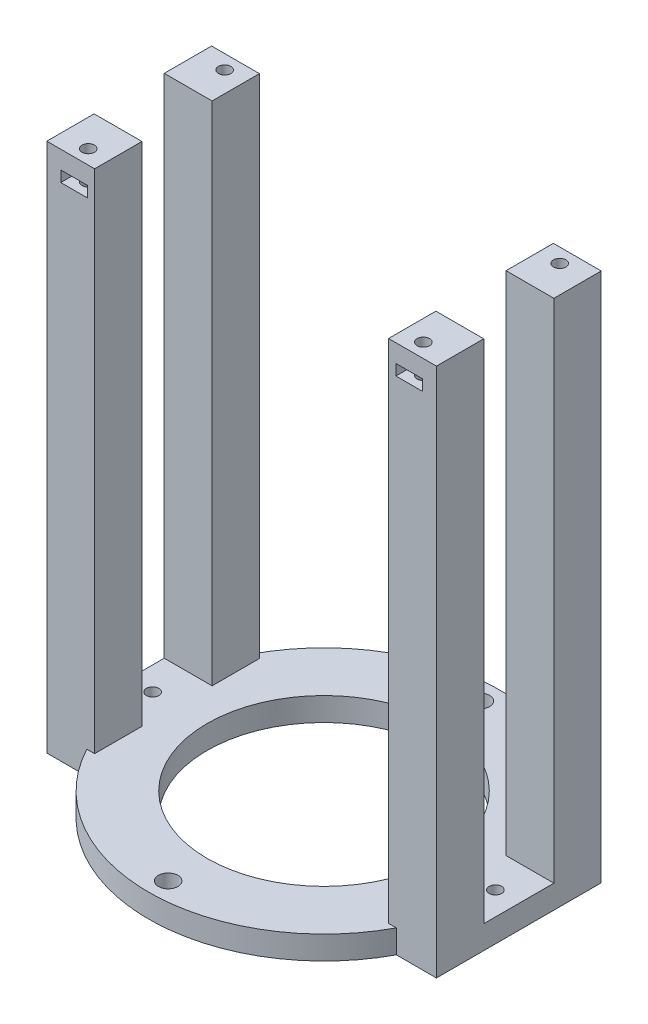
SolidWorks part; units mm, degrees
ref_plane "Front Plane" through (0, 0, 0) normal (0, 0, 1) x (1, 0, 0)
ref_plane "Top Plane" through (0, 0, 0) normal (0, 1, 0) x (1, 0, 0)
ref_plane "Right Plane" through (0, 0, 0) normal (1, 0, 0) x (0, 0, -1)
sketch "Sketch1" plane through (0, 0, 0) normal (0, 1, 0) x (1, 0, 0)
  line L0 (33, 0) -> (-33, 0) construction
  line L2 (-16, 21.15) -> (-50, 21.15)
  line L3 (-16, 21.15) -> (-16, -21.15)
  line L4 (-16, -21.15) -> (-50, -21.15)
  line L5 (-50, 21.15) -> (-50, -21.15)
  line L6 (-16, 21.15) -> (-50, -21.15) construction
  line L7 (-16, -21.15) -> (-50, 21.15) construction
  line L8 (16, 21.15) -> (50, 21.15)
  line L9 (16, 21.15) -> (16, -21.15)
  line L10 (16, -21.15) -> (50, -21.15)
  line L11 (50, 21.15) -> (50, -21.15)
  line L12 (16, 21.15) -> (50, -21.15) construction
  line L13 (16, -21.15) -> (50, 21.15) construction
  circle A0 centre (0, 0) radius 45
  point P6 (0, 0)
  dimension "D1" = 90
  dimension "D2" = 66
  dimension "D3" = 42.3
  dimension "D4" = 42.3
  dimension "D5" = 34
  dimension "D6" = 34
extrude "body" add sketch "Sketch1" along normal blind 6 contours A0 L2 L5 L4 | L2 A0 L4 L3 | L8 A0 L2 L3 L4 L10 L9 | L10 A0 L8 L9 | A0 L10 L11 L8 region at (-29.6863, 0, 0) region at (0, 0, 0) region at (-46.4607, 0, 0) region at (29.6863, 0, 0) region at (46.4607, 0, 0)
sketch "Sketch2" plane through (0, 6, 0) normal (0, 1, 0) x (1, 0, 0)
  line L0 (39.72, -21.15) -> (39.72, 21.15)
  line L1 (-50, 21.15) -> (-39.72, 21.15)
  line L2 (-50, 21.15) -> (-50, -21.15)
  line L3 (-50, -21.15) -> (-39.72, -21.15)
  line L4 (-39.72, 21.15) -> (-39.72, -21.15)
  line L5 (50, 21.15) -> (39.72, 21.15)
  line L6 (50, 21.15) -> (50, -21.15)
  line L7 (50, -21.15) -> (39.72, -21.15)
  line L8 (39.72, 21.15) -> (39.72, -21.15)
  line L9 (39.72, -21.15) -> (37.72, -21.15)
  line L10 (39.72, 21.15) -> (37.72, 21.15)
  line L11 (37.72, -21.15) -> (37.72, 21.15)
  line L12 (-39.72, -21.15) -> (-39.72, 21.15)
  line L13 (-39.72, -21.15) -> (-37.72, -21.15)
  line L14 (-39.72, 21.15) -> (-37.72, 21.15)
  line L15 (-37.72, -21.15) -> (-37.72, 21.15)
  line M6 (39.72, -21.15) -> (50, -21.15)
  line M7 (50, -21.15) -> (50, 21.15)
  line M8 (50, 21.15) -> (39.72, 21.15)
  dimension "D1" = 2
  dimension "D2" = 2
extrude "wings" add sketch "Sketch2" along normal blind 130 contours L8 M8 M6 M7 | L2 L1 L4 L3 | L12 L13 L15 L14 | L0 L9 L11 L10 region at (44.86, 6, 0)
sketch "Sketch3" plane through (0, 136, 0) normal (0, 1, 0) x (1, 0, 0)
  line L0 (43, 0) -> (-43, 0) construction
  line L1 (43, -17.5) -> (43, 17.5) construction
  line L2 (-43, -17.5) -> (-43, 17.5) construction
  circle A0 centre (43, -17.5) radius 1.6
  circle A1 centre (-43, -17.5) radius 1.6
  circle A2 centre (-43, 17.5) radius 1.6
  circle A3 centre (43, 17.5) radius 1.6
  point P4 (0, 0)
  point P8 (43, 0)
  point P11 (-43, 0)
  dimension "D4" = 3.2
  dimension "D5" = 3.2
  dimension "D6" = 3.2
  dimension "D7" = 3.2
  dimension "D1" = 86
  dimension "D2" = 35
  dimension "D3" = 35
extrude "mounting-bore" cut sketch "Sketch3" against normal through all
sketch "Sketch5" plane through (50, 0, 0) normal (1, 0, 0) x (0, 0, -1)
  line L0 (0, 0) -> (0, 6)
  line L1 (21.15, 0) -> (-21.15, 0) construction
  line L2 (9, 6) -> (-9, 6)
  line L3 (9, 6) -> (-9, 6)
  line L4 (9, 6) -> (9, 136)
  line L5 (-9, 6) -> (-9, 136)
  line L6 (9, 136) -> (-9, 136)
  point P7 (0, 6)
  line M9 (21.15, 136) -> (-21.15, 136)
  dimension "D1" = 6
  dimension "D2" = 18
  dimension "D3" = 130
extrude "cut-excess-material" cut sketch "Sketch5" against normal through all contours L5 L2 L4 M9 region at (50, 71, 0)
sketch "Sketch6" plane through (0, 0, 0) normal (0, -1, 0) x (1, 0, 0)
  line L0 (-44, 0) -> (44, 0)
  circle A0 centre (-44, 0) radius 1.6
  circle A1 centre (44, 0) radius 1.6
  point P4 (0, 0)
  dimension "D2" = 3.2
  dimension "D3" = 3.2
  dimension "D1" = 88
extrude "cut-battery-mount" cut sketch "Sketch6" against normal up to next contours A0 | A1 region at (44, 0, 1.5547) region at (-45.5547, 0, 0)
sketch "Sketch8" plane through (0, 0, 21.15) normal (0, 0, 1) x (1, 0, 0)
  line L1 (37.72, 136) -> (50, 136) construction
  line L2 (43, 136) -> (43, 130)
  line L3 (37.72, 136) -> (43, 136)
  line L4 (39.6, 131.4) -> (46.4, 131.4)
  line L5 (39.6, 131.4) -> (39.6, 128.6)
  line L6 (39.6, 128.6) -> (46.4, 128.6)
  line L7 (46.4, 131.4) -> (46.4, 128.6)
  line L8 (39.6, 131.4) -> (46.4, 128.6) construction
  line L9 (39.6, 128.6) -> (46.4, 131.4) construction
  dimension "D2" = 6
  dimension "D3" = 6.8
  dimension "D4" = 2.8
extrude "capture-nut-1" cut sketch "Sketch8" against normal blind 7.3 contours L5 L4 L7 L6
pattern_circular "CirPattern1" count 2 over 360 about axis through (0, 6, 0) along (0, 1, 0) of "capture-nut-1"
sketch "Sketch10" plane through (0, 0, -21.15) normal (0, 0, -1) x (-1, 0, 0)
  line L1 (-50, 136) -> (-37.72, 136) construction
  line L2 (-43, 136) -> (-43, 130)
  line L3 (-43, 136) -> (-37.72, 136)
  line L4 (-46.4, 131.4) -> (-39.6, 131.4)
  line L5 (-46.4, 131.4) -> (-46.4, 128.6)
  line L6 (-46.4, 128.6) -> (-39.6, 128.6)
  line L7 (-39.6, 131.4) -> (-39.6, 128.6)
  line L8 (-46.4, 131.4) -> (-39.6, 128.6) construction
  line L9 (-46.4, 128.6) -> (-39.6, 131.4) construction
  dimension "D2" = 6
  dimension "D3" = 6.8
  dimension "D4" = 2.8
extrude "capture-nut-2" cut sketch "Sketch10" against normal blind 7.3 contours L7 L4 L5 L6 region at (44.7, 131.3265, -21.15)
pattern_circular "CirPattern2" count 2 over 360 about axis through (0, 6, 0) along (0, 1, 0) of "capture-nut-2"
sketch "Sketch11" plane through (0, 0, 0) normal (0, -1, 0) x (1, 0, 0)
  circle A0 centre (0, 0) radius 30
  dimension "D1" = 60
extrude "cut-center-hole" cut sketch "Sketch11" against normal up to next
sketch "Sketch12" plane through (0, 0, 0) normal (0, -1, 0) x (1, 0, 0)
  line L0 (0, 40) -> (0, -40)
  circle A0 centre (0, -40) radius 2.5
  circle A1 centre (0, 40) radius 2.5
  point P5 (0, 0)
  dimension "D2" = 5
  dimension "D3" = 5
  dimension "D1" = 80
extrude "cut-harness-mount" cut sketch "Sketch12" against normal up to next contours A1 | A0 region at (1.7178, 0, -38.2822) region at (-1.7178, 0, 41.7178)
equation "\"th\"= 6mm"
equation "\"D1@body\"=\"th\""
equation "\"wing\"= 130mm"
equation "\"D1@wings\"=\"wing\""
equation "\"D1@Sketch5\"=\"th\""
equation "\"D3@Sketch5\"=\"wing\""
equation "\"capture_nut_depth\"= 7.3mm"
equation "\"capture_nut_height\"= 2.8mm"
equation "\"capture_nut_width\"= 6.8mm"
equation "\"D3@Sketch8\"=\"capture_nut_width\""
equation "\"D4@Sketch8\"=\"capture_nut_height\""
equation "\"D1@capture-nut-1\" = \"capture_nut_depth\""
equation "\"D3@Sketch10\"=\"capture_nut_width\""
equation "\"D4@Sketch10\"=\"capture_nut_height\""
equation "\"D1@capture-nut-2\" = \"capture_nut_depth\""
